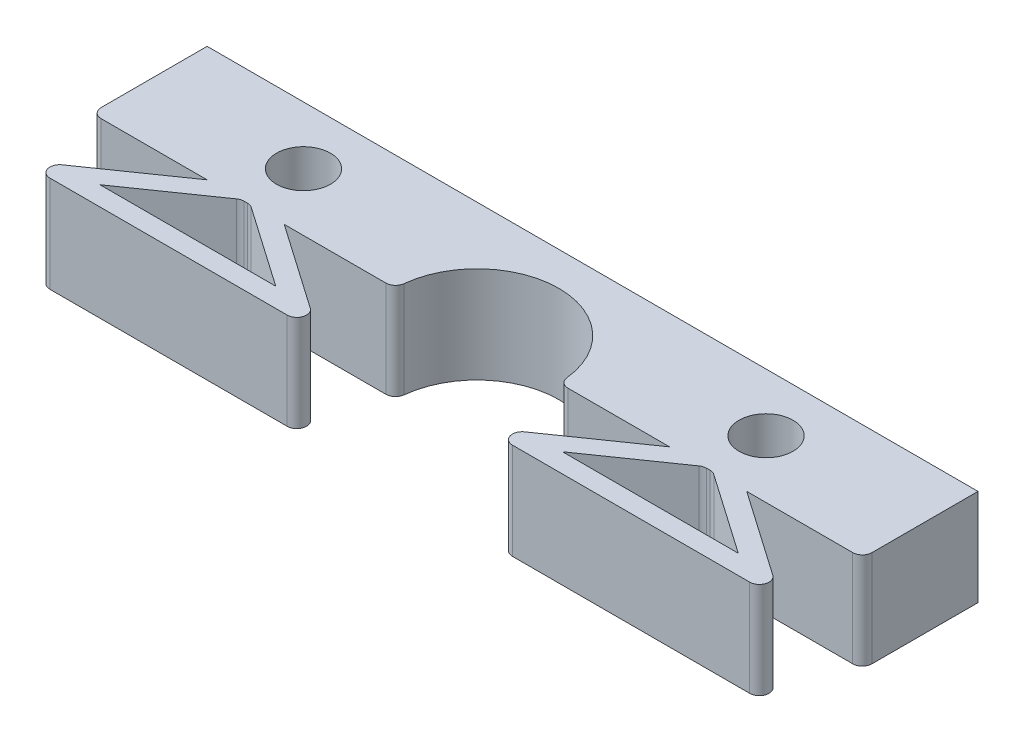
SolidWorks part; units mm, degrees
ref_plane "Front Plane" through (0, 0, 0) normal (0, 0, 1) x (1, 0, 0)
ref_plane "Top Plane" through (0, 0, 0) normal (0, 1, 0) x (1, 0, 0)
ref_plane "Right Plane" through (0, 0, 0) normal (1, 0, 0) x (0, 0, -1)
sketch "Sketch1" plane through (0, 0, 0) normal (0, 1, 0) x (1, 0, 0)
  line L1 (-20, 6) -> (20, 6)
  line L2 (20, 6) -> (20, 0)
  line L8 (4.25, -4) -> (10, 0)
  line L9 (10, 0) -> (-10, 0)
  line L10 (19.75, -4) -> (14, 0)
  line L11 (14, 0) -> (20, 0)
  line L15 (12.2489, 0) -> (11.7511, 0)
  line L17 (11.7511, 0) -> (7.4386, -3)
  line L18 (7.4386, -3) -> (16.5614, -3)
  line L19 (16.5614, -3) -> (12.2489, 0)
  line L20 (4.25, -4) -> (19.75, -4)
  line L21 (0, 6) -> (0, 0) construction
  line L23 (0, 0) -> (0, 20.8018) construction
  line L24 (-4.25, -4) -> (-10, 0)
  line L25 (-12.2489, 0) -> (-11.7511, 0)
  line L26 (-11.7511, 0) -> (-7.4386, -3)
  line L27 (-7.4386, -3) -> (-16.5614, -3)
  line L28 (-16.5614, -3) -> (-12.2489, 0)
  line L29 (-4.25, -4) -> (-19.75, -4)
  line L30 (-19.75, -4) -> (-14, 0)
  line L31 (-14, 0) -> (-20, 0)
  line L32 (-20, 6) -> (-20, 0)
  circle A0 centre (12, 3) radius 1.4
  circle A1 centre (-12, 3) radius 1.4
  point P0 (12, -4)
  point P1 (12, -3)
  point P4 (12, 0)
  dimension "D10" = 2.8
  dimension "D1" = 20
  dimension "D2" = 4.25
  dimension "D3" = 6
  dimension "D4" = 1
  dimension "D5" = 6
  dimension "D6" = 1
  dimension "D7" = 4
  dimension "D9" = 3
  dimension "D11" = 12
extrude "Boss-Extrude1" add sketch "Sketch1" along normal blind 5
sketch "Sketch2" plane through (0, 5, 0) normal (0, 1, 0) x (1, 0, 0)
  line L0 (-10, 0) -> (10, 0) construction
  line L1 (-4.25, 0) -> (4.25, 0)
  arc A0 (-4.25, 0) -> (4.25, 0) centre (0, 0) cw
  dimension "D1" = 4.25
extrude "Cut-Extrude1" cut sketch "Sketch2" against normal through all
fillet "Fillet1" radius 0.5 12 edges at (19.75, 2.5, 4) (4.25, 2.5, 4) (-4.25, 2.5, 4) (-19.75, 2.5, 4) (20, 2.5, 0) (4.25, 2.5, 0) (-4.25, 2.5, 0) (-20, 2.5, 0) (-11.7511, 2.5, 0) (-12.2489, 2.5, 0) (12.2489, 2.5, 0) (11.7511, 2.5, 0)
